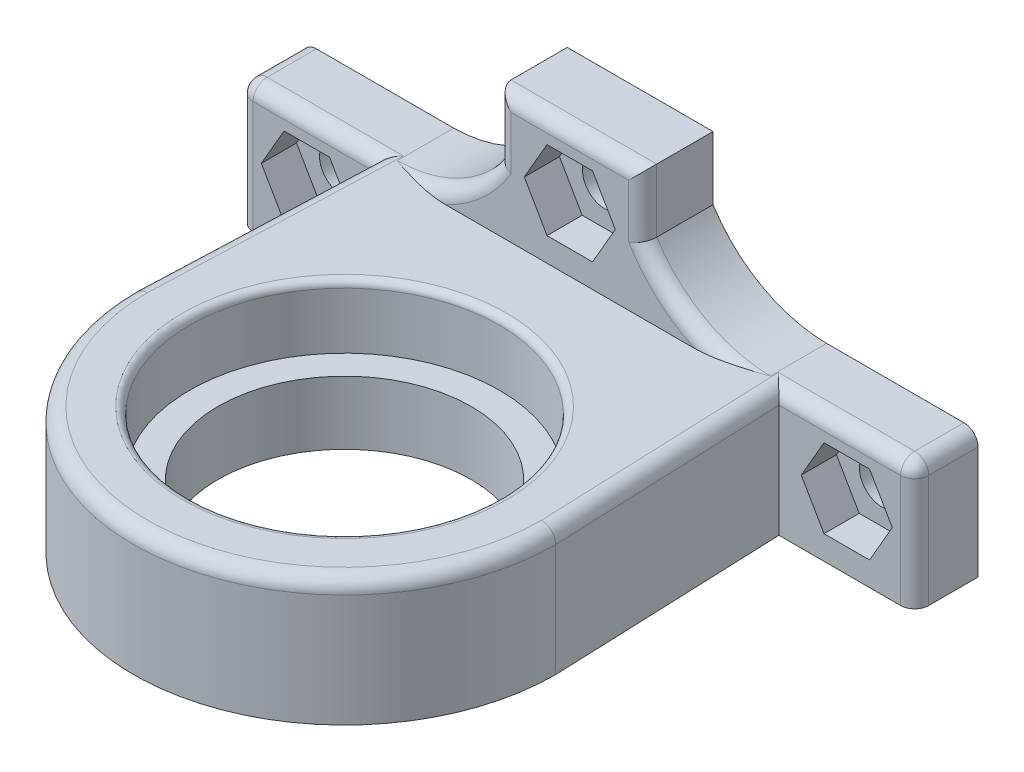
SolidWorks part; units mm, degrees
ref_plane "Alzado" through (0, 0, 0) normal (0, 0, 1) x (1, 0, 0)
ref_plane "Planta" through (0, 0, 0) normal (0, 1, 0) x (1, 0, 0)
ref_plane "Vista lateral" through (0, 0, 0) normal (1, 0, 0) x (0, 0, -1)
sketch "Croquis1" plane through (0, 0, 0) normal (0, 1, 0) x (1, 0, 0)
  line L0 (-12.5027, 9.6432) -> (-13.1455, -6.8568)
  line L1 (-13.1455, 14.1432) -> (16.8545, 14.1432)
  line L2 (1.8545, -6.8568) -> (1.8545, 30.0374) construction
  line L3 (-13.1455, 14.1432) -> (-20.1455, 14.1432)
  line L4 (16.8545, 9.6432) -> (16.2116, 9.6432)
  line L5 (-13.1455, 9.6432) -> (-20.1455, 9.6432)
  line L6 (16.2116, 9.6432) -> (16.8545, -6.8568)
  line L8 (-13.1455, 9.6432) -> (-12.5027, 9.6432)
  line L9 (16.8545, 14.1432) -> (23.8545, 14.1432)
  line L11 (16.8545, 9.6432) -> (23.8545, 9.6432)
  line L12 (23.8545, 14.1432) -> (25.8545, 14.1432)
  line L13 (-20.1455, 14.1432) -> (-22.1455, 14.1432)
  line L15 (-20.1455, 9.6432) -> (-22.1455, 9.6432)
  line L16 (-22.1455, 14.1432) -> (-22.1455, 9.6432)
  line L17 (23.8545, 9.6432) -> (25.8545, 9.6432)
  line L18 (25.8545, 14.1432) -> (25.8545, 9.6432)
  circle A0 centre (1.8545, -6.8568) radius 11
  circle A1 centre (1.8545, -6.8568) radius 15
  circle A2 centre (1.8545, -6.8568) radius 9
  dimension "D3" = 22
  dimension "D7" = 2
  dimension "D9" = 18
  dimension "D1" = 30
  dimension "D2" = 21
  dimension "D5" = 7
  dimension "D6" = 4.5
  dimension "D8" = 2
  dimension "D4" = 4
extrude "Saliente-Extruir2" add sketch "Croquis1" along normal blind 9 contours A0 A1 | A2 A0 | A1 L2 L1 L3 L5 L8 L0 | L2 A1 L6 L4 L11 L9 L1 region at (-9.3794, 0, -9.7639) region at (9.4126, 0, -0.7014) region at (-8.0431, 0, -3.8432) region at (13.0883, 0, -9.7639)
sketch "Croquis2" plane through (0, 9, 0) normal (0, 1, 0) x (1, 0, 0)
  circle A0 centre (1.8545, -6.8568) radius 9 construction
  circle A1 centre (1.8545, -6.8568) radius 9
  circle A2 centre (1.8545, -6.8568) radius 11
extrude "Cortar-Extruir1" cut sketch "Croquis2" against normal blind 4.5
sketch "Croquis3" plane through (0, 0, -9.6432) normal (0, 0, 1) x (1, 0, 0)
  line L0 (-12.5027, 9) -> (-22.1455, 0) construction
  line L2 (-14.0909, 4.5) -> (-15.7075, 7.3)
  line L3 (-15.7075, 7.3) -> (-18.9407, 7.3)
  line L12 (-18.9407, 7.3) -> (-20.5573, 4.5)
  line L13 (-20.5573, 4.5) -> (-18.9407, 1.7)
  line L14 (-18.9407, 1.7) -> (-15.7075, 1.7)
  line L15 (-15.7075, 1.7) -> (-14.0909, 4.5)
  circle A0 centre (-17.3241, 4.5) radius 2.8 construction
  dimension "D2" = 5.6
extrude "Cortar-Extruir3" cut sketch "Croquis3" against normal blind 2.5
sketch "Croquis4" plane through (0, 0, -9.6432) normal (0, 0, 1) x (1, 0, 0)
  line L0 (25.8545, 9) -> (16.2116, 0) construction
  line L1 (16.2116, 9) -> (16.2116, 0) construction
  line L2 (25.8545, 0) -> (16.2116, 0) construction
  line L4 (24.2662, 4.5) -> (22.6496, 7.3)
  line L5 (22.6496, 7.3) -> (19.4165, 7.3)
  line L6 (19.4165, 7.3) -> (17.7999, 4.5)
  line L7 (17.7999, 4.5) -> (19.4165, 1.7)
  line L8 (19.4165, 1.7) -> (22.6496, 1.7)
  line L9 (22.6496, 1.7) -> (24.2662, 4.5)
  circle A0 centre (21.033, 4.5) radius 2.8 construction
  dimension "D1" = 5.6
extrude "Cortar-Extruir4" cut sketch "Croquis4" against normal blind 2.5
sketch "Croquis5" plane through (0, 0, -12.1432) normal (0, 0, 1) x (1, 0, 0)
  line L0 (17.7999, 4.5) -> (24.2662, 4.5) construction
  line L1 (-20.5573, 4.5) -> (-14.0909, 4.5) construction
  circle A0 centre (21.033, 4.5) radius 1.6
  circle A1 centre (-17.3241, 4.5) radius 1.6
extrude "Cortar-Extruir5" cut sketch "Croquis5" against normal blind 2.5
sketch "Croquis6" plane through (0, 9, 0) normal (0, 1, 0) x (1, 0, 0)
  line L2 (-22.1455, 14.1432) -> (25.8545, 14.1432) construction
  line L7 (-22.1455, 14.1432) -> (25.8545, 14.1432)
  line L10 (1.8545, 14.1432) -> (1.8545, 11.6432) construction
  line L12 (-3.3225, 9.1432) -> (7.0314, 9.1432)
  line L13 (-3.3225, 9.1432) -> (-3.3225, 14.1432)
  line L14 (-3.3225, 14.1432) -> (7.0314, 14.1432)
  line L15 (7.0314, 9.1432) -> (7.0314, 14.1432)
  line L16 (-3.3225, 9.1432) -> (7.0314, 14.1432) construction
  line L17 (-3.3225, 14.1432) -> (7.0314, 9.1432) construction
  dimension "D1" = 5
extrude "Saliente-Extruir3" add sketch "Croquis6" along normal blind 9 contours L12 L15 L7 L13 region at (1.8545, 9, -11.6432)
sketch "Croquis7" plane through (0, 0, -9.1432) normal (0, 0, 1) x (1, 0, 0)
  line L0 (7.0314, 18) -> (-3.3225, 9) construction
  line L1 (-3.3225, 18) -> (7.0314, 18) construction
  circle A0 centre (1.8545, 13.5) radius 1.6
extrude "Cortar-Extruir6" cut sketch "Croquis7" against normal blind 9
sketch "Croquis8" plane through (0, 0, -9.1432) normal (0, 0, 1) x (1, 0, 0)
  line L1 (5.0876, 13.5) -> (3.471, 16.3)
  line L2 (3.471, 16.3) -> (0.2379, 16.3)
  line L3 (0.2379, 16.3) -> (-1.3787, 13.5)
  line L4 (-1.3787, 13.5) -> (0.2379, 10.7)
  line L5 (0.2379, 10.7) -> (3.471, 10.7)
  line L6 (3.471, 10.7) -> (5.0876, 13.5)
  circle A0 centre (1.8545, 13.5) radius 2.8 construction
  dimension "D1" = 5.6
extrude "Cortar-Extruir7" cut sketch "Croquis8" against normal blind 2.5
sketch "Croquis12" plane through (0, 0, -14.1432) normal (0, 0, -1) x (-1, 0, 0)
  line L0 (22.1455, 9) -> (3.3225, 9) construction
  line L1 (3.3225, 18) -> (3.3225, 9) construction
  line L3 (-7.0314, 18) -> (-7.0314, 9) construction
  line L4 (-7.0314, 9) -> (-25.8545, 9) construction
  line L5 (11.3894, 9) -> (3.3225, 9)
  line L6 (3.3225, 13.5) -> (3.3225, 9)
  line L8 (-7.0314, 13.5) -> (-7.0314, 9)
  line L9 (-7.0314, 9) -> (-15.0984, 9)
  line L10 (-1.8545, 18) -> (-1.8545, 5.2926) construction
  arc A0 (-7.0314, 13.5) -> (-15.0984, 9) centre (-15.2013, 18.6652) cw
  arc A1 (3.3225, 13.5) -> (11.3894, 9) centre (11.4924, 18.6652) ccw
extrude "Saliente-Extruir5" add sketch "Croquis12" against normal blind 5
fillet "Redondeo2" radius 0.5 1 edges at (1.8545, 9, 17.8568)
fillet "Redondeo3" radius 1 14 edges at (-22.1455, 4.5, -9.6432) (-22.1455, 9, -11.8932) (16.533, 9, -1.3932) (1.8545, 9, 21.8568) (-12.8241, 9, -1.3932) (-17.3241, 9, -9.6432) (-6.7836, 10.224, -9.1432) (-3.3225, 15.75, -9.1432) (1.8545, 18, -9.1432) (7.0314, 15.75, -9.1432) (10.4925, 10.224, -9.1432) (25.8545, 4.5, -9.6432) (25.8545, 9, -11.8932) (21.033, 9, -9.6432)
